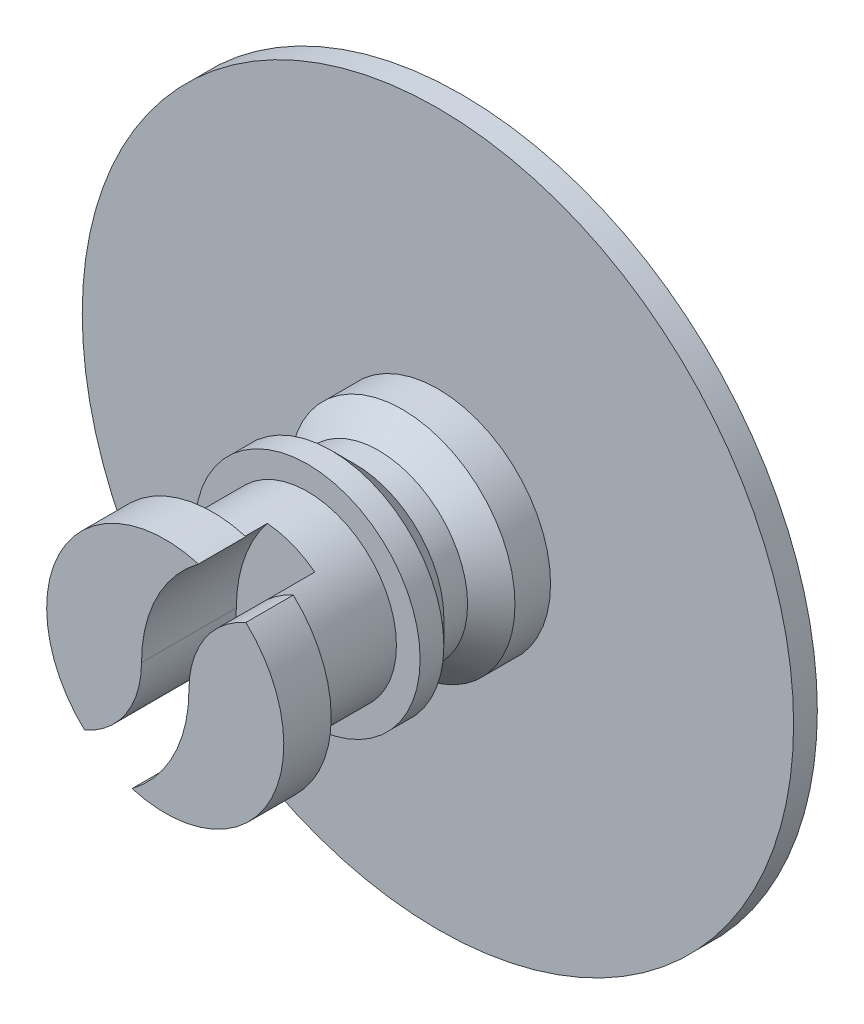
SolidWorks part; units mm, degrees
ref_plane "Спереди" through (0, 0, 0) normal (0, 0, 1) x (1, 0, 0)
ref_plane "Сверху" through (0, 0, 0) normal (0, 1, 0) x (1, 0, 0)
ref_plane "Справа" through (0, 0, 0) normal (1, 0, 0) x (0, 0, -1)
sketch "Эскиз1" plane through (0, 0, 0) normal (0, 0, 1) x (1, 0, 0)
  circle A0 centre (0, 0) radius 7.5
  dimension "D1" = 15
extrude "Бобышка-Вытянуть1" add sketch "Эскиз1" along normal blind 14 and the other way blind 2
sketch "Эскиз2" plane through (0, 0, 0) normal (0, 0, 1) x (1, 0, 0)
  circle A0 centre (0, 0) radius 9.5
  dimension "D1" = 19
extrude "Бобышка-Вытянуть2" add sketch "Эскиз2" along normal blind 2 from offset 2
sketch "Эскиз5" plane through (0, 0, 0) normal (0, 0, 1) x (1, 0, 0)
  circle A0 centre (0, 0) radius 10
  dimension "D1" = 20
extrude "Бобышка-Вытянуть3" add sketch "Эскиз5" along normal blind 4 from offset 12
sketch "Эскиз9" plane through (0, 0, 0) normal (0, 0, 1) x (1, 0, 0)
  line L0 (0, -1000) -> (0, 49000) construction
  line L1 (2, -999.8394) -> (2, 49000.1606) construction
  line L2 (-2, -1000.2983) -> (-2, 48999.7017) construction
  line L3 (-1000, 0) -> (49000, 0) construction
  circle A9 centre (0, 0) radius 15
  arc A10 (9.05, 11.9623) -> (-2, 0) centre (10, 0) ccw
  arc A11 (13.05, 7.3958) -> (2, 0) centre (10, 0) ccw
  arc A12 (-13.05, -7.3958) -> (-2, 0) centre (-10, 0) ccw
  arc A13 (-9.05, -11.9623) -> (2, 0) centre (-10, 0) ccw
  dimension "D1" = 30
  dimension "D5" = 10
  dimension "D2" = 2
  dimension "D3" = 2
extrude "Вырез-Вытянуть3" cut sketch "Эскиз9" along normal blind 8 from offset 8 contours A9 A13 A11 A10 A12 region at (0, 0, 0)
sketch "Эскиз12" plane through (0, 0, 0) normal (1, 0, 0) x (0, 0, -1)
  line L0 (-2, 9.5) -> (0, 7.5)
  line L1 (0, 33) -> (0, -33) construction
  line L2 (2, 7.5) -> (-2, 7.5) construction
  line L3 (0, 7.5) -> (-2, 7.5)
  line L4 (-2, -9.5) -> (-2, 9.5) construction
  line L5 (-2, 7.5) -> (-2, 9.5)
  line L6 (0, 0) -> (-6.2922, 0) construction
revolve "Повернуть1" add sketch "Эскиз12" angle 360 about L6
sketch "Эскиз13" plane through (0, 0, 0) normal (1, 0, 0) x (0, 0, -1)
  line L0 (-2, 9.5) -> (7.2712, 9.5) construction
  line L8 (0, 0) -> (-6.5791, 0) construction
  line L11 (2, 7.5) -> (4, 9.5)
  line L13 (4, 9.5) -> (7, 9.5)
  line L17 (2, -7.5) -> (2, 7.5) construction
  line L21 (2, 0) -> (9, 0)
  line L22 (9, 0) -> (9, 30)
  line L23 (9, 30) -> (7, 30)
  line L24 (7, 30) -> (7, 9.5)
  line L25 (2, 7.5) -> (2, 0)
  dimension "D1" = 3
  dimension "D2" = 2
  dimension "D3" = 2
  dimension "D4" = 30
revolve "Повернуть2" add sketch "Эскиз13" angle 360 about L8
